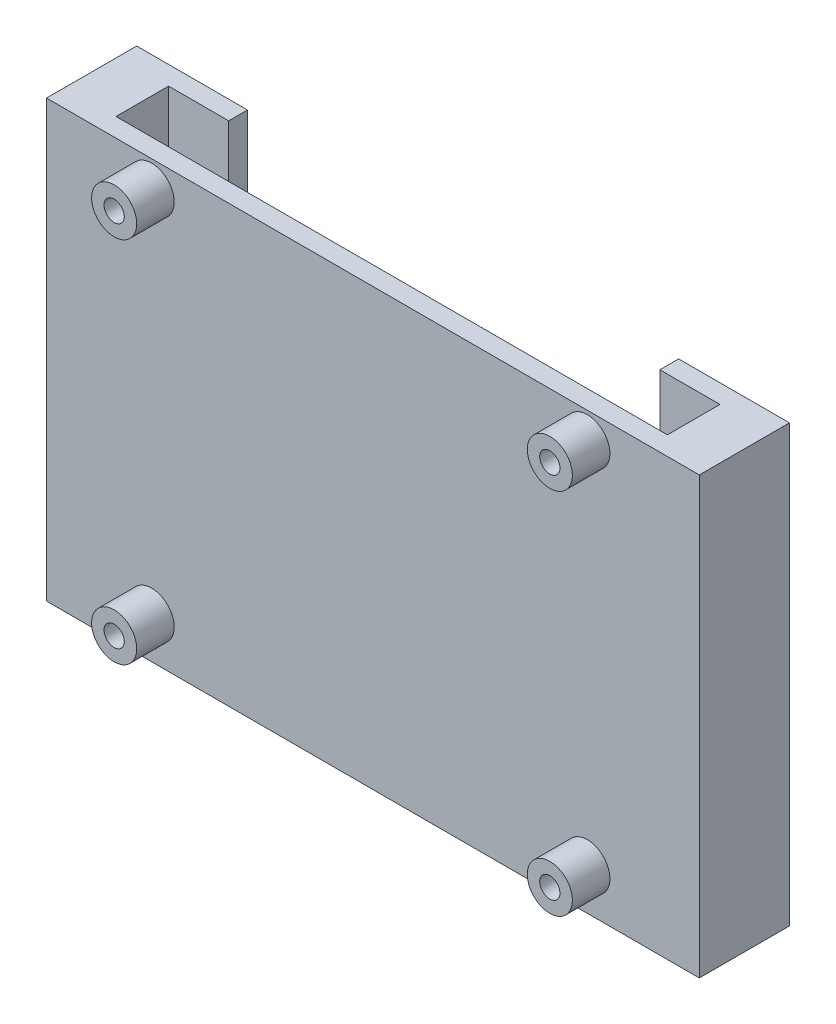
SolidWorks part; units mm, degrees
ref_plane "Front Plane" through (0, 0, 0) normal (0, 0, 1) x (1, 0, 0)
ref_plane "Top Plane" through (0, 0, 0) normal (0, 1, 0) x (1, 0, 0)
ref_plane "Right Plane" through (0, 0, 0) normal (1, 0, 0) x (0, 0, -1)
sketch "Sketch1" plane through (0, 0, 0) normal (0, 0, 1) x (1, 0, 0)
  line L1 (-43.45, -29) -> (43.45, -29)
  line L2 (-43.45, -29) -> (-43.45, 29)
  line L3 (-43.45, 29) -> (43.45, 29)
  line L4 (43.45, -29) -> (43.45, 29)
  line L5 (-43.45, -29) -> (43.45, 29) construction
  line L6 (-43.45, 29) -> (43.45, -29) construction
  point P0 (0, 0)
  dimension "D1" = 86.9
  dimension "D2" = 58
extrude "Boss-Extrude1" add sketch "Sketch1" along normal blind 2.5
sketch "Sketch2" plane through (0, 0, 2.5) normal (0, 0, 1) x (1, 0, 0)
  line L0 (43.45, 29) -> (-43.45, 29) construction
  line L1 (-43.45, 29) -> (-43.45, -29) construction
  circle A0 centre (-29.45, 25.5) radius 3
  circle A1 centre (28.55, 25.5) radius 3
  dimension "D1" = 6
  dimension "D4" = 58
  dimension "D2" = 3.5
  dimension "D3" = 14
extrude "Boss-Extrude2" add sketch "Sketch2" along normal blind 5
pattern_linear "LPattern1" count 2 spacing 49 along (0, -1, 0) of "Boss-Extrude2"
sketch "Sketch3" plane through (0, 0, 7.5) normal (0, 0, 1) x (1, 0, 0)
  circle A0 centre (-29.45, -23.5) radius 3 construction
  circle A1 centre (28.55, 25.5) radius 3 construction
  circle A2 centre (28.55, -23.5) radius 3 construction
  point P0 (-29.45, 25.5)
  point P3 (-29.45, -23.5)
  point P10 (28.55, 25.5)
  point P12 (28.55, -23.5)
hole_wizard "M2.5 Clearance Hole1" positions "Sketch3" profile "Sketch4" hole size "M2.5" standard "ANSI Metric" end condition through all
sketch "Sketch4" plane through (-29.45, 25.5, 7.5) normal (1, 0, 0) x (0, -1, 0)
  line L0 (0, 0) -> (0, 7.5)
  line L1 (0, 7.5) -> (1.35, 7.5)
  line L2 (1.35, 7.5) -> (1.35, 0)
  line L5 (1.35, 0) -> (0, 0)
  line L11 (0, -6.35) -> (0, 107.95) construction
  dimension "Thru Hole Dia." = 2.7
  dimension "Thru Hole Depth" = 7.5
sketch "Sketch6" plane through (0, 0, 0) normal (0, 0, -1) x (-1, 0, 0)
  line L0 (43.45, -29) -> (-43.45, -29) construction
  line L1 (-43.45, 29) -> (-36.7, 29)
  line L2 (-43.45, 29) -> (-43.45, -29)
  line L3 (-43.45, -29) -> (-36.7, -29)
  line L4 (-36.7, 29) -> (-36.7, -29)
  line L6 (43.45, 29) -> (36.7, 29)
  line L7 (43.45, 29) -> (43.45, -29)
  line L8 (43.45, -29) -> (36.7, -29)
  line L9 (36.7, 29) -> (36.7, -29)
  dimension "D1" = 6.75
  dimension "D2" = 6.75
extrude "Boss-Extrude3" add sketch "Sketch6" along normal blind 9.5
sketch "Sketch7" plane through (36.7, 0, 0) normal (-1, 0, 0) x (0, 0, 1)
  line L0 (2.5, -29) -> (-9.5, -29) construction
  line L1 (-9.5, 29) -> (-7, 29)
  line L2 (-9.5, 29) -> (-9.5, -29)
  line L3 (-9.5, -29) -> (-7, -29)
  line L4 (-7, 29) -> (-7, -29)
  dimension "D1" = 2.5
extrude "Boss-Extrude4" add sketch "Sketch7" along normal blind 8
sketch "Sketch8" plane through (-36.7, 0, 0) normal (1, 0, 0) x (0, 0, -1)
  line L1 (9.5, 29) -> (7, 29)
  line L2 (9.5, 29) -> (9.5, -29)
  line L3 (9.5, -29) -> (7, -29)
  line L4 (7, 29) -> (7, -29)
extrude "Boss-Extrude5" add sketch "Sketch8" along normal blind 8
sketch "Sketch9" plane through (0, -29, 0) normal (0, -1, 0) x (1, 0, 0)
  line L0 (-43.45, -3.5) -> (43.45, -3.5) construction
  line L1 (-43.45, 2.5) -> (-43.45, -9.5) construction
  line L2 (43.45, 2.5) -> (43.45, -9.5) construction
  line L3 (-36.7, 0) -> (-43.45, 0) construction
  line L4 (-40.075, 0) -> (-40.075, -9.5) construction
  line L5 (-28.7, -9.5) -> (-43.45, -9.5) construction
  line L6 (36.7, 0) -> (43.45, 0) construction
  line L7 (40.075, 0) -> (40.075, -9.5) construction
  line L8 (43.45, -9.5) -> (28.7, -9.5) construction
  circle A0 centre (-40.075, -3.5) radius 3.15
  circle A1 centre (40.075, -3.5) radius 3.15
  dimension "D1" = 6.3
  dimension "D2" = 6.3
extrude "Cut-Extrude1" cut sketch "Sketch9" against normal blind 2.7
